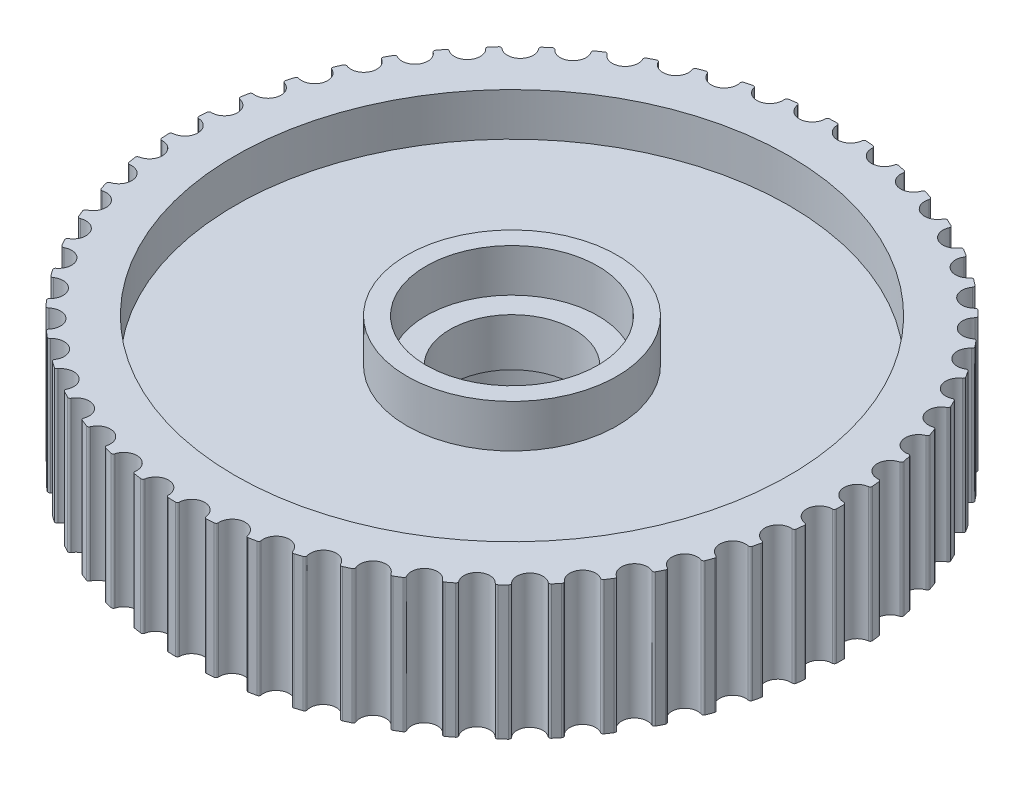
SolidWorks part; units mm, degrees
ref_plane "Front Plane" through (0, 0, 0) normal (0, 0, 1) x (1, 0, 0)
ref_plane "Top Plane" through (0, 0, 0) normal (0, 1, 0) x (1, 0, 0)
ref_plane "Right Plane" through (0, 0, 0) normal (1, 0, 0) x (0, 0, -1)
sketch "Sketch1" plane through (0, 0, 0) normal (0, 1, 0) x (1, 0, 0)
  line L0 (-2.5785, 17.0562) -> (-2.1984, 17.1093)
  line L1 (-0.6166, 17.239) -> (-0.2328, 17.2484)
  line L2 (1.3534, 17.1969) -> (1.7357, 17.1626)
  line L3 (3.3058, 16.9306) -> (3.6817, 16.8529)
  line L4 (5.215, 16.4434) -> (5.5797, 16.3234)
  line L5 (7.0563, 15.7418) -> (7.4049, 15.581)
  line L6 (8.8056, 14.8349) -> (9.1336, 14.6354)
  line L7 (10.4402, 13.7344) -> (10.7433, 13.4988)
  line L8 (11.9386, 12.4549) -> (12.2129, 12.1862)
  line L9 (13.2814, 11.0128) -> (13.5233, 10.7147)
  line L10 (14.4511, 9.4271) -> (14.6574, 9.1033)
  line L11 (15.4324, 7.7184) -> (15.6004, 7.3732)
  line L12 (16.2125, 5.9089) -> (16.3401, 5.5469)
  line L13 (16.7813, 4.0224) -> (16.8668, 3.6481)
  line L14 (17.1313, 2.0833) -> (17.1735, 1.7017)
  line L15 (17.258, 0.1169) -> (17.2565, -0.267)
  line L16 (17.1597, -1.8511) -> (17.1144, -2.2323)
  line L17 (16.8377, -3.7951) -> (16.7493, -4.1686)
  line L18 (16.2962, -5.6896) -> (16.1658, -6.0507)
  line L19 (15.5423, -7.5102) -> (15.3716, -7.854)
  line L20 (14.5858, -9.2329) -> (14.377, -9.555)
  line L21 (13.4391, -10.8353) -> (13.195, -11.1315)
  line L22 (12.1173, -12.2966) -> (11.8409, -12.563)
  line L23 (10.6375, -13.5977) -> (10.3325, -13.8309)
  line L24 (9.019, -14.7216) -> (8.6895, -14.9185)
  line L25 (7.2829, -15.6537) -> (6.9331, -15.8118)
  line L26 (5.452, -16.3818) -> (5.0864, -16.499)
  line L27 (3.5499, -16.8965) -> (3.1734, -16.9712)
  line L28 (1.6016, -17.1909) -> (1.219, -17.2223)
  line L29 (-0.3676, -17.2614) -> (-0.7513, -17.249)
  line L30 (-2.332, -17.107) -> (-2.7117, -17.0509)
  line L31 (-4.2659, -16.7296) -> (-4.6368, -16.6306)
  line L32 (-6.1443, -16.1343) -> (-6.5015, -15.9936)
  line L33 (-7.9425, -15.3287) -> (-8.2813, -15.1482)
  line L34 (-9.6372, -14.3233) -> (-9.9532, -14.1054)
  line L35 (-11.2062, -13.1314) -> (-11.4954, -12.8789)
  line L36 (-12.6292, -11.7684) -> (-12.8877, -11.4845)
  line L37 (-13.8875, -10.252) -> (-14.1119, -9.9405)
  line L38 (-14.9647, -8.6021) -> (-15.1522, -8.2671)
  line L39 (-15.8469, -6.8401) -> (-15.9949, -6.4859)
  line L40 (-16.5224, -4.9891) -> (-16.6291, -4.6204)
  line L41 (-16.9825, -3.0731) -> (-17.0465, -2.6946)
  line L42 (-17.2213, -1.1172) -> (-17.2417, -0.7339)
  line L43 (-17.2355, 0.8532) -> (-17.2121, 1.2363)
  line L44 (-17.025, 2.8123) -> (-16.9581, 3.1903)
  line L45 (-16.5926, 4.7347) -> (-16.483, 5.1027)
  line L46 (-15.9438, 6.5953) -> (-15.793, 6.9483)
  line L47 (-15.0872, 8.3698) -> (-14.8971, 8.7034)
  line L48 (-14.0339, 10.0351) -> (-13.8071, 10.3448)
  line L49 (-12.7976, 11.5695) -> (-12.537, 11.8513)
  line L50 (-11.3945, 12.9529) -> (-11.1034, 13.2032)
  line L51 (-9.8428, 14.1674) -> (-9.5251, 14.3828)
  line L52 (-8.1628, 15.1971) -> (-7.8226, 15.3749)
  line L53 (-6.3764, 16.0285) -> (-6.0182, 16.1664)
  line L54 (-4.5069, 16.651) -> (-4.1352, 16.7471)
  circle A0 centre (0, 0) radius 14.5
  circle A1 centre (0, 0) radius 16.5 construction
  circle A2 centre (0, 0) radius 17.25 construction
  circle A3 centre (0, 0) radius 17.53 construction
  arc A4 (-2.1984, 17.1093) -> (-2.0744, 17.0174) centre (-2.1831, 17.0004) cw
  arc A5 (-2.0744, 17.0174) -> (-0.7227, 17.1282) centre (-1.4026, 17.1226) ccw
  arc A6 (-0.7227, 17.1282) -> (-0.6166, 17.239) centre (-0.6127, 17.129) cw
  arc A7 (-0.2328, 17.2484) -> (-0.1202, 17.143) centre (-0.2301, 17.1385) cw
  arc A8 (-0.1202, 17.143) -> (1.2354, 17.0989) centre (0.5592, 17.171) ccw
  arc A9 (1.2354, 17.0989) -> (1.3534, 17.1969) centre (1.3448, 17.0873) cw
  arc A10 (1.7357, 17.1626) -> (1.8356, 17.045) centre (1.7259, 17.053) cw
  arc A11 (1.8356, 17.045) -> (3.1774, 16.8467) centre (2.5138, 16.9953) ccw
  arc A12 (3.1774, 16.8467) -> (3.3058, 16.9306) centre (3.2847, 16.8226) cw
  arc A13 (3.6817, 16.8529) -> (3.7675, 16.7247) centre (3.6594, 16.7452) cw
  arc A14 (3.7675, 16.7247) -> (5.0779, 16.3747) centre (4.4356, 16.598) ccw
  arc A15 (5.0779, 16.3747) -> (5.215, 16.4434) centre (5.1818, 16.3386) cw
  arc A16 (5.5797, 16.3234) -> (5.6503, 16.1862) centre (5.5453, 16.2189) cw
  arc A17 (5.6503, 16.1862) -> (6.9123, 15.6892) centre (6.2996, 15.9842) ccw
  arc A18 (6.9123, 15.6892) -> (7.0563, 15.7418) centre (7.0114, 15.6414) cw
  arc A19 (7.4049, 15.581) -> (7.4594, 15.4367) centre (7.3588, 15.4811) cw
  arc A20 (7.4594, 15.4367) -> (8.6565, 14.799) centre (8.0815, 15.162) ccw
  arc A21 (8.6565, 14.799) -> (8.8056, 14.8349) centre (8.7495, 14.7403) cw
  arc A22 (9.1336, 14.6354) -> (9.1713, 14.4858) centre (9.0764, 14.5414) cw
  arc A23 (9.1713, 14.4858) -> (10.2879, 13.7158) centre (9.758, 14.142) ccw
  arc A24 (10.2879, 13.7158) -> (10.4402, 13.7344) centre (10.3736, 13.6468) cw
  arc A25 (10.7433, 13.4988) -> (10.7637, 13.3459) centre (10.6758, 13.412) cw
  arc A26 (10.7637, 13.3459) -> (11.7852, 12.4537) centre (11.3074, 12.9375) ccw
  arc A27 (11.7852, 12.4537) -> (11.9386, 12.4549) centre (11.8625, 12.3754) cw
  arc A28 (12.2129, 12.1862) -> (12.2157, 12.032) centre (12.1359, 12.1077) cw
  arc A29 (12.2157, 12.032) -> (13.1289, 11.0291) centre (12.7093, 11.5642) ccw
  arc A30 (13.1289, 11.0291) -> (13.2814, 11.0128) centre (13.1968, 10.9426) cw
  arc A31 (13.5233, 10.7147) -> (13.5085, 10.5611) centre (13.4378, 10.6454) cw
  arc A32 (13.5085, 10.5611) -> (14.3014, 9.4607) centre (13.9456, 10.0401) ccw
  arc A33 (14.3014, 9.4607) -> (14.4511, 9.4271) centre (14.359, 9.3669) cw
  arc A34 (14.6574, 9.1033) -> (14.6252, 8.9524) centre (14.5646, 9.0442) cw
  arc A35 (14.6252, 8.9524) -> (15.2875, 7.7688) centre (15, 8.3851) ccw
  arc A36 (15.2875, 7.7688) -> (15.4324, 7.7184) centre (15.334, 7.6691) cw
  arc A37 (15.6004, 7.3732) -> (15.5513, 7.227) centre (15.5015, 7.3251) cw
  arc A38 (15.5513, 7.227) -> (16.0743, 5.9756) centre (15.859, 6.6206) ccw
  arc A39 (16.0743, 5.9756) -> (16.2125, 5.9089) centre (16.1092, 5.8712) cw
  arc A40 (16.3401, 5.5469) -> (16.2746, 5.4072) centre (16.2363, 5.5103) cw
  arc A41 (16.2746, 5.4072) -> (16.6516, 4.1043) centre (16.5111, 4.7696) ccw
  arc A42 (16.6516, 4.1043) -> (16.7813, 4.0224) centre (16.6743, 3.9967) cw
  arc A43 (16.8668, 3.6481) -> (16.7858, 3.5168) centre (16.7595, 3.6236) cw
  arc A44 (16.7858, 3.5168) -> (17.0118, 2.1794) centre (16.9481, 2.8565) ccw
  arc A45 (17.0118, 2.1794) -> (17.1313, 2.0833) centre (17.0221, 2.0699) cw
  arc A46 (17.1735, 1.7017) -> (17.0781, 1.5805) centre (17.0642, 1.6896) cw
  arc A47 (17.0781, 1.5805) -> (17.1502, 0.2261) centre (17.1641, 0.9059) ccw
  arc A48 (17.1502, 0.2261) -> (17.258, 0.1169) centre (17.148, 0.1161) cw
  arc A49 (17.2565, -0.267) -> (17.1478, -0.3766) centre (17.1465, -0.2666) cw
  arc A50 (17.1478, -0.3766) -> (17.0651, -1.7303) centre (17.1564, -1.0565) ccw
  arc A51 (17.0651, -1.7303) -> (17.1597, -1.8511) centre (17.0503, -1.8393) cw
  arc A52 (17.1144, -2.2323) -> (16.994, -2.3288) centre (17.0052, -2.2193) cw
  arc A53 (16.994, -2.3288) -> (16.7575, -3.6643) centre (16.925, -3.0053) ccw
  arc A54 (16.7575, -3.6643) -> (16.8377, -3.7951) centre (16.7304, -3.7709) cw
  arc A55 (16.7493, -4.1686) -> (16.6187, -4.2507) centre (16.6422, -4.1433) cw
  arc A56 (16.6187, -4.2507) -> (16.2314, -5.5506) centre (16.473, -4.915) ccw
  arc A57 (16.2314, -5.5506) -> (16.2962, -5.6896) centre (16.1923, -5.6534) cw
  arc A58 (16.1658, -6.0507) -> (16.0267, -6.1174) centre (16.0623, -6.0133) cw
  arc A59 (16.0267, -6.1174) -> (15.4938, -7.3646) centre (15.8062, -6.7607) ccw
  arc A60 (15.4938, -7.3646) -> (15.5423, -7.5102) centre (15.4432, -7.4623) cw
  arc A61 (15.3716, -7.854) -> (15.2258, -7.9044) centre (15.2731, -7.8051) cw
  arc A62 (15.2258, -7.9044) -> (14.5542, -9.0827) centre (14.9334, -8.5183) ccw
  arc A63 (14.5542, -9.0827) -> (14.5858, -9.2329) centre (14.4928, -9.1741) cw
  arc A64 (14.377, -9.555) -> (14.2264, -9.5884) centre (14.2847, -9.4952) cw
  arc A65 (14.2264, -9.5884) -> (13.4248, -10.6826) centre (13.8659, -10.1651) ccw
  arc A66 (13.4248, -10.6826) -> (13.4391, -10.8353) centre (13.3535, -10.7663) cw
  arc A67 (13.195, -11.1315) -> (13.0415, -11.1476) centre (13.1101, -11.0616) cw
  arc A68 (13.0415, -11.1476) -> (12.1205, -12.1432) centre (12.6177, -11.6794) ccw
  arc A69 (12.1205, -12.1432) -> (12.1173, -12.2966) centre (12.04, -12.2182) cw
  arc A70 (11.8409, -12.563) -> (11.6867, -12.5615) centre (11.7646, -12.4839) cw
  arc A71 (11.6867, -12.5615) -> (10.6581, -13.4457) centre (11.205, -13.0415) ccw
  arc A72 (10.6581, -13.4457) -> (10.6375, -13.5977) centre (10.5697, -13.511) cw
  arc A73 (10.3325, -13.8309) -> (10.1795, -13.8118) centre (10.2657, -13.7435) cw
  arc A74 (10.1795, -13.8118) -> (9.0568, -14.5729) centre (9.6462, -14.2338) ccw
  arc A75 (9.0568, -14.5729) -> (9.019, -14.7216) centre (8.9615, -14.6278) cw
  arc A76 (8.6895, -14.9185) -> (8.5396, -14.8821) centre (8.633, -14.8241) cw
  arc A77 (8.5396, -14.8821) -> (7.3375, -15.5103) centre (7.9617, -15.2405) ccw
  arc A78 (7.3375, -15.5103) -> (7.2829, -15.6537) centre (7.2365, -15.5539) cw
  arc A79 (6.9331, -15.8118) -> (6.7883, -15.7585) centre (6.8878, -15.7115) cw
  arc A80 (6.7883, -15.7585) -> (5.5225, -16.2456) centre (6.1734, -16.0487) ccw
  arc A81 (5.5225, -16.2456) -> (5.452, -16.3818) centre (5.4172, -16.2774) cw
  arc A82 (5.0864, -16.499) -> (4.9486, -16.4296) centre (5.0528, -16.3943) cw
  arc A83 (4.9486, -16.4296) -> (3.6355, -16.7692) centre (4.3046, -16.6478) ccw
  arc A84 (3.6355, -16.7692) -> (3.5499, -16.8965) centre (3.5273, -16.7888) cw
  arc A85 (3.1734, -16.9712) -> (3.0444, -16.8865) centre (3.152, -16.8633) cw
  arc A86 (3.0444, -16.8865) -> (1.7012, -17.0743) centre (2.3797, -17.0299) ccw
  arc A87 (1.7012, -17.0743) -> (1.6016, -17.1909) centre (1.5914, -17.0814) cw
  arc A88 (1.219, -17.2223) -> (1.1005, -17.1235) centre (1.21, -17.1127) cw
  arc A89 (1.1005, -17.1235) -> (-0.2554, -17.1568) centre (0.4238, -17.1902) ccw
  arc A90 (-0.2554, -17.1568) -> (-0.3676, -17.2614) centre (-0.3652, -17.1515) cw
  arc A91 (-0.7513, -17.249) -> (-0.8577, -17.1373) centre (-0.7477, -17.139) cw
  arc A92 (-0.8577, -17.1373) -> (-2.2085, -17.0159) centre (-1.5376, -17.1264) ccw
  arc A93 (-2.2085, -17.0159) -> (-2.332, -17.107) centre (-2.3171, -16.998) cw
  arc A94 (-2.7117, -17.0509) -> (-2.8047, -16.9278) centre (-2.6956, -16.9421) cw
  arc A95 (-2.8047, -16.9278) -> (-4.1329, -16.6532) centre (-3.479, -16.8395) ccw
  arc A96 (-4.1329, -16.6532) -> (-4.2659, -16.7296) centre (-4.2387, -16.623) cw
  arc A97 (-4.6368, -16.6306) -> (-4.7152, -16.4977) centre (-4.6084, -16.5243) cw
  arc A98 (-4.7152, -16.4977) -> (-6.0034, -16.0735) centre (-5.3749, -16.3331) ccw
  arc A99 (-6.0034, -16.0735) -> (-6.1443, -16.1343) centre (-6.1051, -16.0315) cw
  arc A100 (-6.5015, -15.9936) -> (-6.5642, -15.8526) centre (-6.4612, -15.8912) cw
  arc A101 (-6.5642, -15.8526) -> (-7.7957, -15.2843) centre (-7.2009, -15.6139) ccw
  arc A102 (-7.7957, -15.2843) -> (-7.9425, -15.3287) centre (-7.8919, -15.231) cw
  arc A103 (-8.2813, -15.1482) -> (-8.3275, -15.001) centre (-8.2296, -15.0511) cw
  arc A104 (-8.3275, -15.001) -> (-9.4863, -14.296) centre (-8.9329, -14.6913) ccw
  arc A105 (-9.4863, -14.296) -> (-9.6372, -14.3233) centre (-9.5758, -14.2321) cw
  arc A106 (-9.9532, -14.1054) -> (-9.9824, -13.9539) centre (-9.8908, -14.0149) cw
  arc A107 (-9.9824, -13.9539) -> (-11.0532, -13.1215) centre (-10.5485, -13.5772) ccw
  arc A108 (-11.0532, -13.1215) -> (-11.2062, -13.1314) centre (-11.1348, -13.0477) cw
  arc A109 (-11.4954, -12.8789) -> (-11.5071, -12.725) centre (-11.423, -12.796) cw
  arc A110 (-11.5071, -12.725) -> (-12.476, -11.7759) centre (-12.0265, -12.2862) ccw
  arc A111 (-12.476, -11.7759) -> (-12.6292, -11.7684) centre (-12.5487, -11.6934) cw
  arc A112 (-12.8877, -11.4845) -> (-12.8817, -11.3304) centre (-12.8063, -11.4105) cw
  arc A113 (-12.8817, -11.3304) -> (-13.7361, -10.277) centre (-13.3478, -10.8352) ccw
  arc A114 (-13.7361, -10.277) -> (-13.8875, -10.252) centre (-13.7989, -10.1867) cw
  arc A115 (-14.1119, -9.9405) -> (-14.0884, -9.7881) centre (-14.0227, -9.8762) cw
  arc A116 (-14.0884, -9.7881) -> (-14.8172, -8.6442) centre (-14.495, -9.243) ccw
  arc A117 (-14.8172, -8.6442) -> (-14.9647, -8.6021) centre (-14.8693, -8.5473) cw
  arc A118 (-15.1522, -8.2671) -> (-15.1115, -8.1183) centre (-15.0562, -8.2134) cw
  arc A119 (-15.1115, -8.1183) -> (-15.7051, -6.8988) centre (-15.4533, -7.5304) ccw
  arc A120 (-15.7051, -6.8988) -> (-15.8469, -6.8401) centre (-15.7458, -6.7966) cw
  arc A121 (-15.9949, -6.4859) -> (-15.9375, -6.3427) centre (-15.8934, -6.4435) cw
  arc A122 (-15.9375, -6.3427) -> (-16.3883, -5.0635) centre (-16.2101, -5.7198) ccw
  arc A123 (-16.3883, -5.0635) -> (-16.5224, -4.9891) centre (-16.4171, -4.9574) cw
  arc A124 (-16.6291, -4.6204) -> (-16.5558, -4.4846) centre (-16.5235, -4.5898) cw
  arc A125 (-16.5558, -4.4846) -> (-16.8577, -3.1624) centre (-16.7555, -3.8346) ccw
  arc A126 (-16.8577, -3.1624) -> (-16.9825, -3.0731) centre (-16.8743, -3.0536) cw
  arc A127 (-17.0465, -2.6946) -> (-16.9582, -2.5682) centre (-16.9381, -2.6763) cw
  arc A128 (-16.9582, -2.5682) -> (-17.1075, -1.2201) centre (-17.0825, -1.8996) ccw
  arc A129 (-17.1075, -1.2201) -> (-17.2213, -1.1172) centre (-17.1115, -1.1102) cw
  arc A130 (-17.2417, -0.7339) -> (-17.1395, -0.6183) centre (-17.1319, -0.728) cw
  arc A131 (-17.1395, -0.6183) -> (-17.1342, 0.738) centre (-17.1869, 0.0601) ccw
  arc A132 (-17.1342, 0.738) -> (-17.2355, 0.8532) centre (-17.1256, 0.8477) cw
  arc A133 (-17.2121, 1.2363) -> (-17.0974, 1.3395) centre (-17.1023, 1.2296) cw
  arc A134 (-17.0974, 1.3395) -> (-16.9375, 2.6864) centre (-17.0671, 2.0189) ccw
  arc A135 (-16.9375, 2.6864) -> (-17.025, 2.8123) centre (-16.9165, 2.7944) cw
  arc A136 (-16.9581, 3.1903) -> (-16.8324, 3.2798) centre (-16.8498, 3.1712) cw
  arc A137 (-16.8324, 3.2798) -> (-16.52, 4.5996) centre (-16.7248, 3.9512) ccw
  arc A138 (-16.52, 4.5996) -> (-16.5926, 4.7347) centre (-16.4868, 4.7045) cw
  arc A139 (-16.483, 5.1027) -> (-16.3479, 5.1772) centre (-16.3776, 5.0713) cw
  arc A140 (-16.3479, 5.1772) -> (-15.8871, 6.4528) centre (-16.1645, 5.832) ccw
  arc A141 (-15.8871, 6.4528) -> (-15.9438, 6.5953) centre (-15.8422, 6.5532) cw
  arc A142 (-15.793, 6.9483) -> (-15.6503, 7.007) centre (-15.6919, 6.9051) cw
  arc A143 (-15.6503, 7.007) -> (-15.0471, 8.2218) centre (-15.3935, 7.6366) ccw
  arc A144 (-15.0471, 8.2218) -> (-15.0872, 8.3698) centre (-14.991, 8.3164) cw
  arc A145 (-14.8971, 8.7034) -> (-14.7487, 8.7453) centre (-14.8016, 8.6489) cw
  arc A146 (-14.7487, 8.7453) -> (-14.0109, 9.8834) centre (-14.4218, 9.3416) ccw
  arc A147 (-14.0109, 9.8834) -> (-14.0339, 10.0351) centre (-13.9444, 9.9711) cw
  arc A148 (-13.8071, 10.3448) -> (-13.6548, 10.3696) centre (-13.7183, 10.2798) cw
  arc A149 (-13.6548, 10.3696) -> (-12.7921, 11.4162) centre (-13.262, 10.9247) ccw
  arc A150 (-12.7921, 11.4162) -> (-12.7976, 11.5695) centre (-12.7161, 11.4957) cw
  arc A151 (-12.537, 11.8513) -> (-12.3829, 11.8586) centre (-12.4562, 11.7766) cw
  arc A152 (-12.3829, 11.8586) -> (-11.4065, 12.8) centre (-11.9294, 12.3653) ccw
  arc A153 (-11.4065, 12.8) -> (-11.3945, 12.9529) centre (-11.3219, 12.8703) cw
  arc A154 (-11.1034, 13.2032) -> (-10.9495, 13.1928) centre (-11.0317, 13.1198) cw
  arc A155 (-10.9495, 13.1928) -> (-9.8722, 14.0168) centre (-10.4412, 13.6446) ccw
  arc A156 (-9.8722, 14.0168) -> (-9.8428, 14.1674) centre (-9.7801, 14.077) cw
  arc A157 (-9.5251, 14.3828) -> (-9.3734, 14.355) centre (-9.4634, 14.2918) cw
  arc A158 (-9.3734, 14.355) -> (-8.2091, 15.0508) centre (-8.8169, 14.7459) ccw
  arc A159 (-8.2091, 15.0508) -> (-8.1628, 15.1971) centre (-8.1108, 15.1002) cw
  arc A160 (-7.8226, 15.3749) -> (-7.675, 15.33) centre (-7.7717, 15.2774) cw
  arc A161 (-7.675, 15.33) -> (-6.4391, 15.8885) centre (-7.0777, 15.6548) ccw
  arc A162 (-6.4391, 15.8885) -> (-6.3764, 16.0285) centre (-6.3358, 15.9263) cw
  arc A163 (-6.0182, 16.1664) -> (-5.8766, 16.105) centre (-5.9786, 16.0638) cw
  arc A164 (-5.8766, 16.105) -> (-4.5851, 16.519) centre (-5.2461, 16.3596) ccw
  arc A165 (-4.5851, 16.519) -> (-4.5069, 16.651) centre (-4.4781, 16.5448) cw
  arc A166 (-4.1352, 16.7471) -> (-4.0016, 16.6699) centre (-4.1077, 16.6406) cw
  arc A167 (-4.0016, 16.6699) -> (-2.6713, 16.934) centre (-3.3462, 16.851) ccw
  arc A168 (-2.6713, 16.934) -> (-2.5785, 17.0562) centre (-2.5621, 16.9474) cw
  point P449 (0.0007, -0.0077)
  dimension "D1" = 29
  dimension "D2" = 33
  dimension "D3" = 34.5
  dimension "D4" = 35.06
  dimension "D5" = 0.11
  dimension "D6" = 0.68
  dimension "D7" = 0.11
  dimension "D8" = 55
extrude "Boss-Extrude1" add sketch "Sketch1" along normal mid plane 7
sketch "Sketch3" plane through (0, 0, 0) normal (0, 1, 0) x (1, 0, 0)
  circle A0 centre (0, 0) radius 3.25
  circle A1 centre (0, 0) radius 4.5
  circle A2 centre (0, 0) radius 5.5
  circle A3 centre (0, 0) radius 14.7155
  point P7 (0, 0)
  point P8 (0, 0)
  dimension "D1" = 6.5
  dimension "D2" = 9
  dimension "D3" = 11
extrude "Boss-Extrude2" add sketch "Sketch3" along normal mid plane 2.5 contours A3 A2 | A1 A0 region at (-4.3727, 0, 0) region at (-14.2993, 0, 0)
extrude "Boss-Extrude3" add sketch "Sketch3<3>" along normal mid plane 7 contours A2 A1 region at (-5.3444, 0, 0)
sketch "Sketch3<3>" plane through (0, 0, 0) normal (0, 1, 0) x (1, 0, 0) same geometry as "Sketch3"
